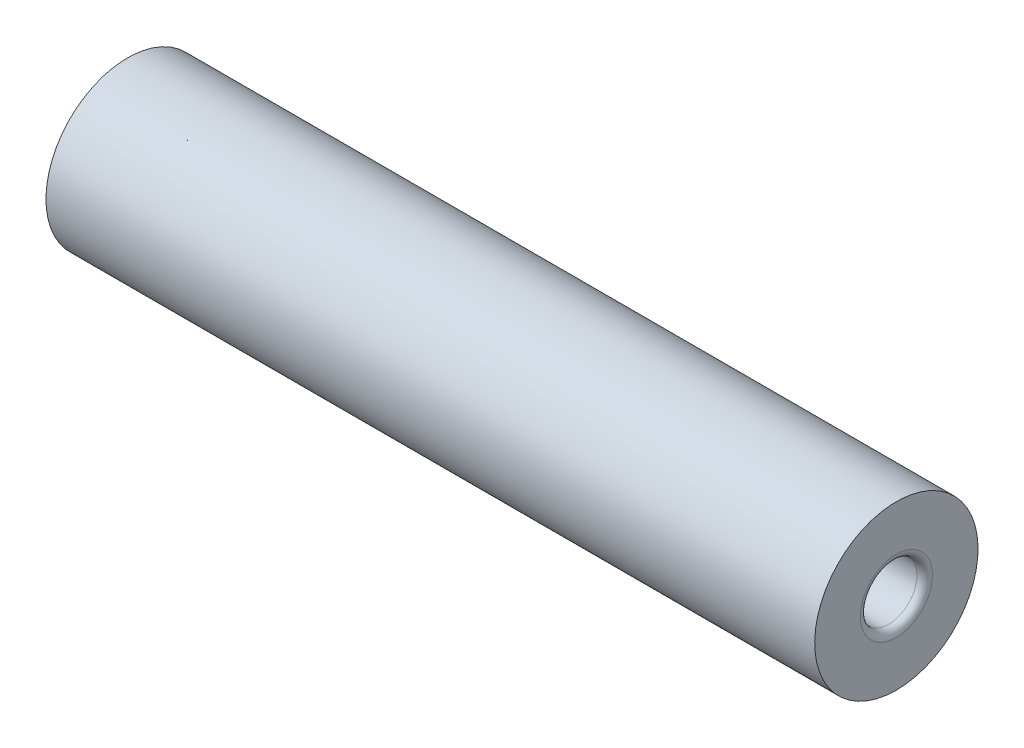
SolidWorks part; units mm, degrees
ref_plane "Front Plane" through (0, 0, 0) normal (0, 0, 1) x (1, 0, 0)
ref_plane "Top Plane" through (0, 0, 0) normal (0, 1, 0) x (1, 0, 0)
ref_plane "Right Plane" through (0, 0, 0) normal (1, 0, 0) x (0, 0, -1)
sketch "Sketch1" plane through (0, 0, 0) normal (0, 0, 1) x (1, 0, 0)
  line L1 (0, 0) -> (50.8, 0) construction
  line L2 (0, 0) -> (0, 5.3975)
  line L3 (0, 5.3975) -> (50.8, 5.3975)
  line L4 (50.8, 0) -> (50.8, 5.3975)
  line L5 (25.4, 5.3975) -> (25.4, 0) construction
  line L7 (12.9075, 0) -> (0, 0)
  line L8 (37.8925, 0) -> (50.8, 0)
  line L11 (12.9075, 0) -> (37.8925, 0)
  point P208 (25.4, 1.5)
  dimension "D1" = 50.8
  dimension "D2" = 5.3975
revolve "Revolve1" add sketch "Sketch1" angle 360 about L3
sketch "Sketch4" plane through (0, 0, 0) normal (-1, 0, 0) x (0, 0, 1)
  point P0 (0, 5.3975)
hole_wizard "Tap Drill for M4x0.7 Tap2" positions "Sketch5" profile "Sketch6" hole size "M4x0.7" standard "ANSI Metric"
sketch "Sketch5" plane through (0, 0, 0) normal (-1, 0, 0) x (0, 0, 1)
  point P0 (0, 5.3975)
sketch "Sketch6" plane through (0, 5.3975, 0) normal (0, 1, 0) x (0, 0, 1)
  line L0 (0, 0) -> (0, 51.9266)
  line L1 (0, 51.9266) -> (1.875, 50.8)
  line L2 (1.875, 50.8) -> (1.875, 0)
  line L5 (1.875, 0) -> (0, 0)
  line L10 (0, 51.9266) -> (-1.875, 50.8) construction
  line L11 (0, -6.35) -> (0, 107.95) construction
  dimension "Hole Dia." = 3.75
  dimension "Hole Depth" = 50.8
  dimension "Drill Angle" = 118
fillet "Fillet1" radius 0.508 2 edges at (0, 5.3975, 1.875) (50.8, 7.2725, 0)
equation "\"arm spacing\"= 2"
equation "\"D1@Sketch1\"=\"arm spacing\""
equation "\"D2@Sketch1\"=\"roller diameter\"/2"
equation "\"symbol room\"= ( ( 35 / 2 ) - 6.5 )"
equation "\"roller diameter\"= .425"
